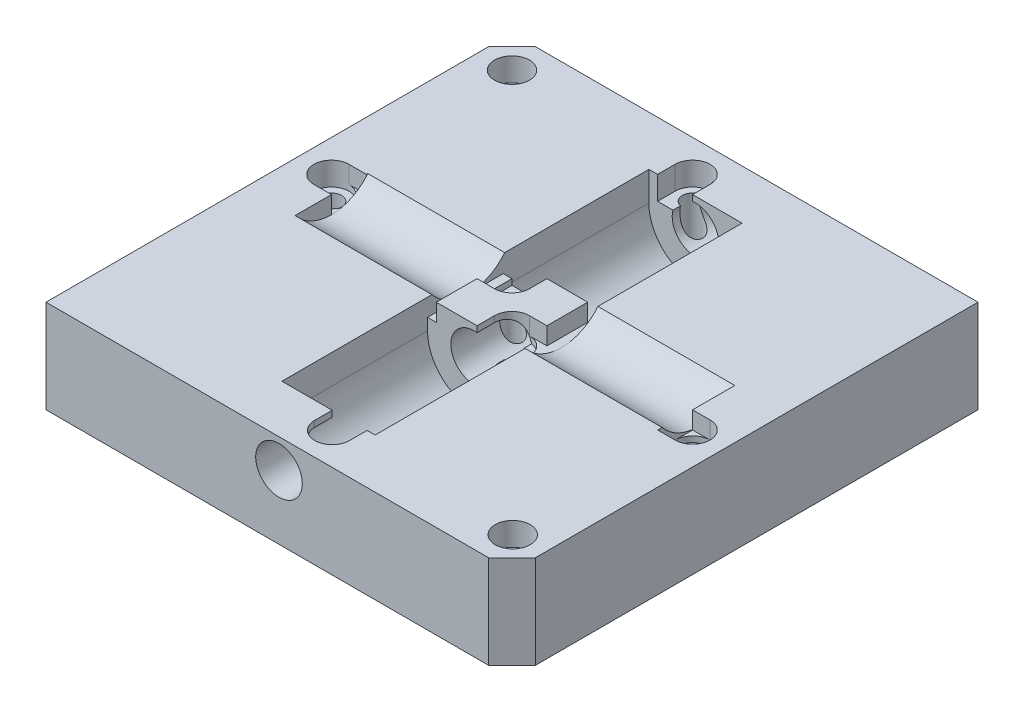
SolidWorks part; units mm, degrees
ref_plane "Front Plane" through (0, 0, 0) normal (0, 0, 1) x (1, 0, 0)
ref_plane "Top Plane" through (0, 0, 0) normal (0, 1, 0) x (1, 0, 0)
ref_plane "Right Plane" through (0, 0, 0) normal (1, 0, 0) x (0, 0, -1)
sketch "Sketch2" plane through (0, 0, 0) normal (0, 1, 0) x (1, 0, 0)
  line L1 (-40, -40) -> (40, -40)
  line L2 (-40, -40) -> (-40, 40)
  line L3 (-40, 40) -> (40, 40)
  line L4 (40, -40) -> (40, 40)
  line L5 (-40, -40) -> (40, 40) construction
  line L6 (-40, 40) -> (40, -40) construction
  point P0 (0, 0)
  dimension "D1" = 80
  dimension "D2" = 80
extrude "Boss-Extrude1" add sketch "Sketch2" along normal blind 16
sketch "Sketch4" plane through (0, 16, 0) normal (0, 1, 0) x (1, 0, 0)
  circle A0 centre (-3.5, 3.5) radius 1.75
  circle A1 centre (3.5, -3.5) radius 1.75
  circle A2 centre (-3.5, 34.5) radius 1.75
  circle A3 centre (-34.5, 34.5) radius 1.75
  circle A4 centre (-34.5, 3.5) radius 1.75
  circle A5 centre (3.6244, -34.5) radius 1.75
  circle A6 centre (34.6244, -34.5) radius 1.75
  circle A7 centre (34.5, -3.5) radius 1.75
  point P0 (3.5, -3.5)
  point P1 (-3.5, 3.5)
  point P2 (-3.5, 34.5)
  point P3 (-34.5, 3.5)
  point P4 (-34.5, 34.5)
  point P5 (34.5, -3.5)
  point P6 (3.6244, -34.5)
  point P7 (34.6244, -34.5)
  dimension "D16" = 3.5
  dimension "D17" = 3.5
  dimension "D18" = 3.5
  dimension "D19" = 3.5
  dimension "D20" = 3.5
  dimension "D21" = 3.5
  dimension "D22" = 3.5
  dimension "D23" = 3.5
  dimension "D1" = 3.5
  dimension "D2" = 3.5
  dimension "D3" = 3.5
  dimension "D4" = 3.5
  dimension "D5" = 31
  dimension "D6" = 31
  dimension "D7" = 0
  dimension "D8" = 0
  dimension "D9" = 31
  dimension "D10" = 31
  dimension "D11" = 31
  dimension "D12" = 31
  dimension "D13" = 31
  dimension "D14" = 31
  dimension "D15" = 0
extrude "Cut-Extrude1" cut sketch "Sketch4" against normal through all both and the other way through all
sketch "Sketch6" plane through (0, 16, 0) normal (0, 1, 0) x (1, 0, 0)
  line L4 (40, -40) -> (40, 40)
  line L5 (40, 40) -> (-40, 40)
  line L6 (-40, 40) -> (-40, -40)
  line L7 (-40, -40) -> (40, -40)
  line L8 (40, -40) -> (40, 40)
  line L9 (40, 40) -> (-40, 40)
  line L10 (-40, 40) -> (-40, -40)
  line L11 (-40, -40) -> (40, -40)
  circle A0 centre (3.6244, -34.5) radius 1.75 construction
  circle A1 centre (34.6244, -34.5) radius 1.75 construction
  circle A2 centre (34.5, -3.5) radius 1.75 construction
  circle A3 centre (3.5, -3.5) radius 1.75 construction
  circle A4 centre (-34.5, 3.5) radius 1.75 construction
  circle A5 centre (-3.5, 3.5) radius 1.75 construction
  circle A6 centre (-3.5, 34.5) radius 1.75 construction
  circle A7 centre (-34.5, 34.5) radius 1.75 construction
  circle A8 centre (3.6244, -34.5) radius 1.75
  circle A9 centre (34.6244, -34.5) radius 1.75
  circle A10 centre (34.5, -3.5) radius 1.75
  circle A11 centre (3.5, -3.5) radius 1.75
  circle A12 centre (-34.5, 3.5) radius 1.75
  circle A13 centre (-3.5, 3.5) radius 1.75
  circle A14 centre (-3.5, 34.5) radius 1.75
  circle A15 centre (-34.5, 34.5) radius 1.75
  circle A16 centre (-3.5, 3.5) radius 3
  circle A17 centre (3.5, -3.5) radius 3
  circle A18 centre (34.5, -3.5) radius 3
  circle A19 centre (34.6244, -34.5) radius 3
  circle A20 centre (3.6244, -34.5) radius 3
  circle A21 centre (-34.5, 3.5) radius 3
  circle A22 centre (-34.5, 34.5) radius 3
  circle A23 centre (-3.5, 34.5) radius 3
  circle M7 centre (-34.5, 34.5) radius 1.75
  dimension "D2" = 6
  dimension "D3" = 6
  dimension "D4" = 6
  dimension "D5" = 6
  dimension "D6" = 6
  dimension "D7" = 6
  dimension "D8" = 6
  dimension "D9" = 6
  dimension "D1" = 0
extrude "Cut-Extrude2" cut sketch "Sketch6" against normal blind 4 contours A22 M7 | M7 | A21 | A23 | A16 | A22 | A17 | A18 | A20 | A19 region at (-34.5, 16, -34.5) region at (-37.4151, 16, -34.5)
chamfer "Chamfer1" distance 4 angle 45 2 edges at (-40, 8, -40) (40, 8, 40)
sketch "Sketch7" plane through (0, 16, 0) normal (0, 1, 0) x (1, 0, 0)
  line L1 (-8, 6.5) -> (8, 6.5)
  line L2 (-8, 6.5) -> (-8, 31.5)
  line L3 (-8, 31.5) -> (8, 31.5)
  line L4 (8, 6.5) -> (8, 31.5)
  line L5 (-8, 6.5) -> (8, 31.5) construction
  line L6 (40, 40) -> (-36, 40)
  line L7 (-36, 40) -> (-40, 36)
  line L8 (-40, 36) -> (-40, -40)
  line L9 (-40, -40) -> (36, -40)
  line L10 (36, -40) -> (40, -36)
  line L11 (40, -36) -> (40, 40)
  line L12 (40, 40) -> (-36, 40)
  line L13 (-36, 40) -> (-40, 36)
  line L14 (-40, 36) -> (-40, -40)
  line L15 (-40, -40) -> (36, -40)
  line L16 (36, -40) -> (40, -36)
  line L17 (40, -36) -> (40, 40)
  line L18 (-8, 31.5) -> (8, 6.5) construction
  line L19 (-6.5, 3.5) -> (-0.5, 3.5)
  line L20 (-6.5, 3.5) -> (-6.5, 6.5)
  line L21 (-6.5, 6.5) -> (-0.5, 6.5)
  line L22 (-0.5, 3.5) -> (-0.5, 6.5)
  line L23 (-6.5, 34.5) -> (-0.5, 34.5)
  line L24 (-6.5, 34.5) -> (-6.5, 31.5)
  line L25 (-6.5, 31.5) -> (-0.5, 31.5)
  line L26 (-0.5, 34.5) -> (-0.5, 31.5)
  circle A0 centre (-3.5, 3.5) radius 3 construction
  circle A1 centre (-3.5, 34.5) radius 3 construction
  circle A2 centre (-3.5, 3.5) radius 3
  circle A3 centre (-3.5, 34.5) radius 3
  point P2 (0, 19)
  circle M12 centre (-3.5, 3.5) radius 3
  circle M13 centre (-3.5, 34.5) radius 3
  dimension "D2" = 16
  dimension "D3" = 0
  dimension "D4" = 25
  dimension "D5" = 19
  dimension "D1" = 0
extrude "Cut-Extrude5" cut sketch "Sketch7" against normal blind 4 contours L24 L3 M13 | L23 M13 | L26 L3 M13 | L1 L4 L3 L2 | L20 L1 M12 | L19 M12 | L22 L1 M12 region at (0, 16, -19) region at (-5.8299, 16, -5.8299) region at (-1.1701, 16, -5.8299) region at (-3.5, 16, -4.7732) region at (-5.8299, 16, -32.1701) region at (-1.1701, 16, -32.1701) region at (-3.5, 16, -33.2268)
sketch "Sketch8" plane through (0, 16, 0) normal (0, 1, 0) x (1, 0, 0)
  line L1 (-8, -31.5) -> (8, -31.5)
  line L2 (-8, -31.5) -> (-8, -6.5)
  line L3 (-8, -6.5) -> (8, -6.5)
  line L4 (8, -31.5) -> (8, -6.5)
  line L5 (-8, -31.5) -> (8, -6.5) construction
  line L6 (40, 40) -> (-36, 40)
  line L7 (-36, 40) -> (-40, 36)
  line L8 (-40, 36) -> (-40, -40)
  line L9 (-40, -40) -> (36, -40)
  line L10 (36, -40) -> (40, -36)
  line L11 (40, -36) -> (40, 40)
  line L12 (40, 40) -> (-36, 40)
  line L13 (-36, 40) -> (-40, 36)
  line L14 (-40, 36) -> (-40, -40)
  line L15 (-40, -40) -> (36, -40)
  line L16 (36, -40) -> (40, -36)
  line L17 (40, -36) -> (40, 40)
  line L18 (-8, -6.5) -> (8, -31.5) construction
  line L19 (6.6244, -34.5) -> (0.6244, -34.5)
  line L20 (6.6244, -34.5) -> (6.6244, -31.5)
  line L21 (6.6244, -31.5) -> (0.6244, -31.5)
  line L22 (0.6244, -34.5) -> (0.6244, -31.5)
  line L23 (0.5, -3.5) -> (6.5, -3.5)
  line L24 (0.5, -3.5) -> (0.5, -6.5)
  line L25 (0.5, -6.5) -> (6.5, -6.5)
  line L26 (6.5, -3.5) -> (6.5, -6.5)
  circle A0 centre (3.6244, -34.5) radius 3 construction
  circle A1 centre (3.5, -3.5) radius 3 construction
  circle A2 centre (3.6244, -34.5) radius 3
  circle A3 centre (3.5, -3.5) radius 3
  point P12 (0, -19)
  dimension "D2" = 25
  dimension "D3" = 19
  dimension "D4" = 16
  dimension "D1" = 0
extrude "Cut-Extrude6" cut sketch "Sketch8" against normal blind 4 contours L22 L23 | L23 L22 | L22 L24 L3 | L26 L22 L3 | L1 L4 L3 L2 | L19 L20 L1 | L19 | L22 L19 L1 | L19 region at (0, 16, 19) region at (1.2945, 16, 32.1701) region at (5.9543, 16, 32.1701) region at (3.6244, 16, 33.2268) region at (3.6244, 16, 35.7732) region at (1.1701, 16, 5.8299) region at (5.8299, 16, 5.8299) region at (3.5, 16, 4.7732) region at (3.5, 16, 2.2268)
sketch "Sketch9" plane through (0, 16, 0) normal (0, 1, 0) x (1, 0, 0)
  line L0 (6.6244, -31.5) -> (8, -31.5) construction
  line L1 (8, -31.5) -> (8, -6.5) construction
  line L2 (-8, -31.5) -> (-8, -6.5) construction
  line L3 (-8, -6.5) -> (0.5, -6.5) construction
  line L4 (-8, 6.5) -> (-6.5, 6.5) construction
  line L5 (-8, 6.5) -> (-8, 31.5) construction
  line L6 (40, 40) -> (-36, 40)
  line L7 (-36, 40) -> (-40, 36)
  line L8 (-40, 36) -> (-40, -40)
  line L9 (-40, -40) -> (36, -40)
  line L10 (36, -40) -> (40, -36)
  line L11 (40, -36) -> (40, 40)
  line L12 (40, 40) -> (-36, 40)
  line L13 (-36, 40) -> (-40, 36)
  line L14 (-40, 36) -> (-40, -40)
  line L15 (-40, -40) -> (36, -40)
  line L16 (36, -40) -> (40, -36)
  line L17 (40, -36) -> (40, 40)
  line L18 (-0.5, 31.5) -> (8, 31.5) construction
  line L19 (8, 6.5) -> (8, 31.5) construction
  line L20 (6.6244, -31.5) -> (8, -31.5)
  line L21 (8, -31.5) -> (8, -6.5)
  line L22 (-8, -31.5) -> (-8, -6.5)
  line L23 (-8, -6.5) -> (0.5, -6.5)
  line L24 (-8, 6.5) -> (-6.5, 6.5)
  line L25 (-8, 6.5) -> (-8, 31.5)
  line L26 (-0.5, 31.5) -> (8, 31.5)
  line L27 (8, 6.5) -> (8, 31.5)
  line L29 (-8, 6.5) -> (8, 6.5)
  line L30 (-8, 6.5) -> (-8, 31.5)
  line L31 (-8, 31.5) -> (8, 31.5)
  line L32 (8, 6.5) -> (8, 31.5)
  line L33 (-8, -31.5) -> (8, -31.5)
  line L34 (-8, -31.5) -> (-8, -6.5)
  line L35 (-8, -6.5) -> (8, -6.5)
  line L36 (8, -31.5) -> (8, -6.5)
  line M8 (-6.5, 6.5) -> (-8, 6.5)
  line M9 (-8, 6.5) -> (-8, 31.5)
  line M10 (-8, 31.5) -> (-6.5, 31.5)
  line M14 (-0.5, 31.5) -> (8, 31.5)
  line M15 (8, 31.5) -> (8, 6.5)
  line M16 (8, 6.5) -> (-0.5, 6.5)
  line M30 (0.6244, -31.5) -> (-8, -31.5)
  line M31 (-8, -31.5) -> (-8, -6.5)
  line M32 (-8, -6.5) -> (0.5, -6.5)
  line M36 (6.5, -6.5) -> (8, -6.5)
  line M37 (8, -6.5) -> (8, -31.5)
  line M38 (8, -31.5) -> (6.6244, -31.5)
  dimension "D1" = 0
extrude "Cut-Extrude7" cut sketch "Sketch9" against normal blind 13 contours L31 L29 M10 M9 M8 M16 M15 M14 | L35 L33 M32 M31 M30 M38 M37 M36 region at (0, 16, 19) region at (0, 16, -19)
fillet "Fillet1" radius 8 4 edges at (8, 3, -19) (-8, 3, -19) (8, 3, 19) (-8, 3, 19)
sketch "Sketch10" plane through (0, 16, 0) normal (0, 1, 0) x (1, 0, 0)
  line L0 (3.5, -0.5) -> (6.5, -0.5)
  line L1 (6.5, -8) -> (31.5, -8)
  line L2 (6.5, -8) -> (6.5, 8)
  line L3 (6.5, 8) -> (31.5, 8)
  line L4 (31.5, -8) -> (31.5, 8)
  line L5 (6.5, -8) -> (31.5, 8) construction
  line L6 (6.5, 8) -> (31.5, -8) construction
  line L8 (-31.5, -8) -> (-6.5, -8)
  line L9 (-31.5, -8) -> (-31.5, 8)
  line L10 (-31.5, 8) -> (-6.5, 8)
  line L11 (-6.5, -8) -> (-6.5, 8)
  line L12 (-31.5, -8) -> (-6.5, 8) construction
  line L13 (-31.5, 8) -> (-6.5, -8) construction
  line L14 (-34.5, 6.5) -> (-31.5, 6.5)
  line L15 (-34.5, 6.5) -> (-34.5, 0.5)
  line L16 (-34.5, 0.5) -> (-31.5, 0.5)
  line L17 (-31.5, 6.5) -> (-31.5, 0.5)
  line L18 (3.5, -0.5) -> (6.5, -0.5)
  line L19 (3.5, -0.5) -> (3.5, -6.5)
  line L20 (3.5, -6.5) -> (6.5, -6.5)
  line L21 (6.5, -0.5) -> (6.5, -6.5)
  line L22 (-3.5, 0.5) -> (-6.5, 0.5)
  line L23 (-3.5, 0.5) -> (-3.5, 6.5)
  line L24 (-3.5, 6.5) -> (-6.5, 6.5)
  line L25 (-6.5, 0.5) -> (-6.5, 6.5)
  line L26 (34.5, -0.5) -> (31.5, -0.5)
  line L27 (34.5, -0.5) -> (34.5, -6.5)
  line L28 (34.5, -6.5) -> (31.5, -6.5)
  line L29 (31.5, -0.5) -> (31.5, -6.5)
  arc A0 (6.5, -3.5) -> (0.5, -3.5) centre (3.5, -3.5) ccw construction
  arc A1 (6.5, -3.5) -> (0.5, -3.5) centre (3.5, -3.5) ccw
  circle A2 centre (-34.5, 3.5) radius 3 construction
  circle A3 centre (34.5, -3.5) radius 3
  circle A4 centre (34.5, -3.5) radius 3
  arc A5 (-6.5, 3.5) -> (-0.5, 3.5) centre (-3.5, 3.5) ccw construction
  circle A6 centre (-34.5, 3.5) radius 3
  arc A7 (-6.5, 3.5) -> (-0.5, 3.5) centre (-3.5, 3.5) ccw
  point P0 (19, 0)
  point P20 (-19, 0)
  line M15 (-6.5, 3.5) -> (-6.5, 6.5)
  line M16 (-6.5, 6.5) -> (-8, 6.5)
  line M17 (-8, 6.5) -> (-8, 31.5)
  line M23 (8, 31.5) -> (8, 6.5)
  line M24 (8, 6.5) -> (-0.5, 6.5)
  arc M26 (-0.5, 3.5) -> (-6.5, 3.5) centre (-3.5, 3.5) cw
  circle M27 centre (-34.5, 3.5) radius 3
  circle M29 centre (34.5, -3.5) radius 3
  line M39 (-8, -31.5) -> (-8, -6.5)
  line M40 (-8, -6.5) -> (0.5, -6.5)
  arc M42 (0.5, -3.5) -> (6.5, -3.5) centre (3.5, -3.5) cw
  line M43 (6.5, -3.5) -> (6.5, -6.5)
  line M44 (6.5, -6.5) -> (8, -6.5)
  line M45 (8, -6.5) -> (8, -31.5)
  dimension "D5" = 0
  dimension "D1" = 16
  dimension "D2" = 25
  dimension "D3" = 19
  dimension "D4" = 0
  dimension "D6" = 25
  dimension "D7" = 19
  dimension "D8" = 16
  dimension "D9" = 0
extrude "Cut-Extrude8" cut sketch "Sketch10" against normal blind 3 contours L27 M29 | L26 L4 M29 | L27 M29 | L28 L4 M29 | L1 L4 L3 L2 M23 M24 M43 M44 M45 | L19 L20 M43 M42 | L2 L0 M42 | L11 L10 L9 L8 M40 M15 M16 M17 M39 | L23 L24 M15 M26 | L22 L11 M26 | L16 L9 M27 | L15 M27 | L14 L9 M27 region at (4.9002, 16, 3.78) region at (5.8299, 16, 1.1701) region at (19.1337, 16, 0) region at (32.1701, 16, 1.1701) region at (32.1701, 16, 5.8299) region at (33.2268, 16, 3.5) region at (35.7732, 16, 3.5) region at (-19.1337, 16, 0) region at (-32.1701, 16, -1.1701) region at (-32.1701, 16, -5.8299) region at (-33.2268, 16, -3.5) region at (-5.8299, 16, -1.1701) region at (-4.9002, 16, -3.78)
sketch "Sketch12" plane through (-31.5, 0, 0) normal (1, 0, 0) x (0, 0, -1)
  line L0 (0.5, 13) -> (8, 13)
  line L1 (8, 16) -> (8, 13)
  line L4 (0.5, 16) -> (-8, 16)
  line L5 (-8, 16) -> (-8, 13)
  line L6 (-8, 13) -> (0.5, 13)
  line L7 (0.5, 13) -> (0.5, 16)
  line L8 (0.5, 16) -> (-8, 16)
  line L9 (-8, 16) -> (-8, 13)
  line L10 (-8, 13) -> (0.5, 13)
  line L11 (0.5, 13) -> (0.5, 16)
  line L12 (8, 16) -> (6.5, 16)
  line L13 (6.5, 16) -> (6.5, 13)
  line L14 (6.5, 13) -> (8, 13)
  line L15 (8, 13) -> (8, 16)
  line L16 (8, 16) -> (6.5, 16)
  line L17 (6.5, 16) -> (6.5, 13)
  line L18 (6.5, 13) -> (8, 13)
  line L19 (8, 13) -> (8, 16)
  circle A0 centre (0.5, 21) radius 8
  line M10 (-8, 16) -> (-8, 13)
  line M11 (-8, 13) -> (0.5, 13)
  dimension "D3" = 16
  dimension "D4" = 8
  dimension "D1" = 0
  dimension "D2" = 0
extrude "Boss-Extrude3" add sketch "Sketch12" along normal blind 23.5 contours A0 L0 L17 | A0 L17 L0 L1 L16 | A0 L8 M10 M11 region at (-31.5, 13.782, -5.0555) region at (-31.5, 14.2083, 5.6741) region at (-31.5, 14.4886, -7.2554)
mirror "Mirror1" about plane through (0, 0, 0) normal (1, 0, 0) of "Boss-Extrude3"
sketch "Sketch13" plane through (0, 0, 6.5) normal (0, 0, 1) x (1, 0, 0)
  line L9 (8, 11) -> (8, 13)
  line L10 (8, 13) -> (6.5, 13)
  line L11 (6.5, 13) -> (6.5, 12)
  line L12 (6.5, 12) -> (0.5, 12)
  line L13 (0.5, 12) -> (0.5, 16)
  line L14 (0.5, 16) -> (-6.5, 16)
  line L15 (-6.5, 16) -> (-6.5, 13)
  line L16 (-6.5, 13) -> (-8, 13)
  line L17 (-8, 13) -> (-8, 11)
  line L18 (8, 11) -> (8, 13)
  line L19 (8, 13) -> (6.5, 13)
  line L20 (6.5, 13) -> (6.5, 12)
  line L21 (6.5, 12) -> (0.5, 12)
  line L22 (0.5, 12) -> (0.5, 16)
  line L23 (0.5, 16) -> (-6.5, 16)
  line L24 (-6.5, 16) -> (-6.5, 13)
  line L25 (-6.5, 13) -> (-8, 13)
  line L26 (-8, 13) -> (-8, 11)
  circle A0 centre (0, 11) radius 4
  arc A2 (-8, 11) -> (0, 3) centre (0, 11) ccw
  arc A3 (0, 3) -> (8, 11) centre (0, 11) ccw
  arc A4 (-8, 11) -> (0, 3) centre (0, 11) ccw
  arc A5 (0, 3) -> (8, 11) centre (0, 11) ccw
  dimension "D2" = 8
  dimension "D1" = 0
extrude "Cut-Extrude9" cut sketch "Sketch13" against normal through all both and the other way through all contours A0
